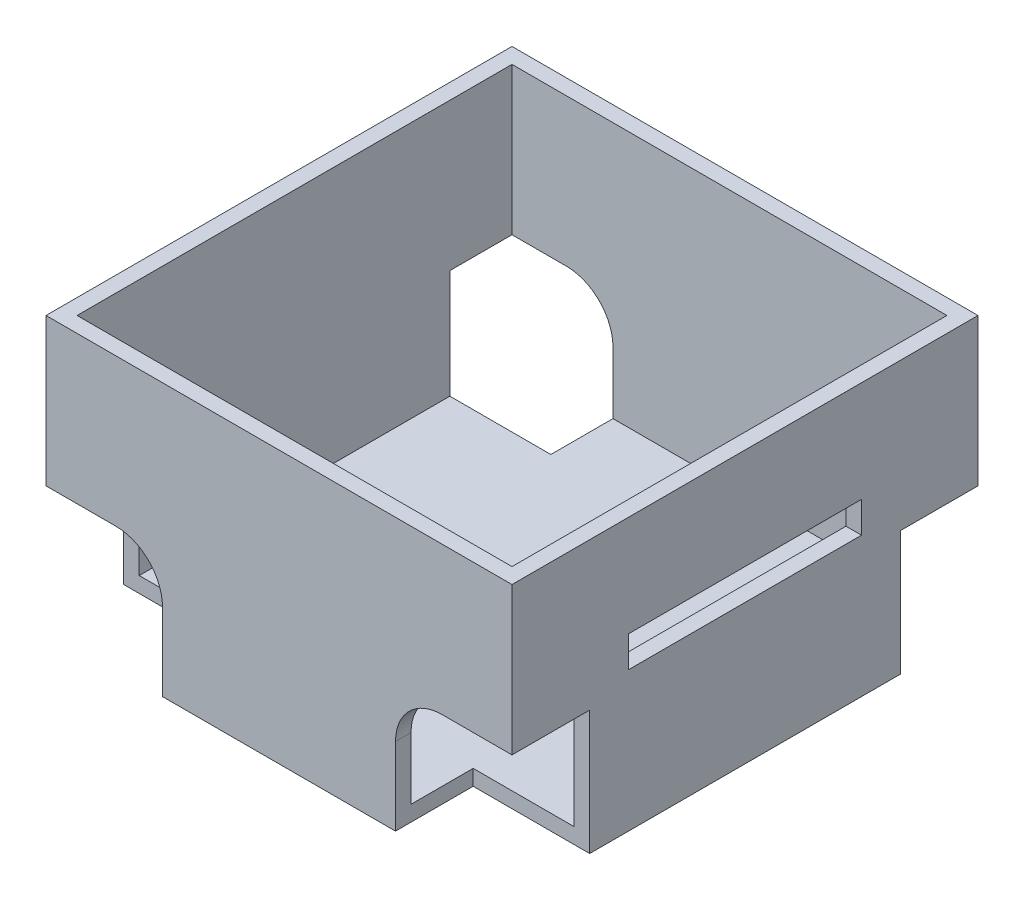
SolidWorks part; units mm, degrees
material "1060 Alloy"
ref_plane "Front Plane" through (0, 0, 0) normal (0, 0, 1) x (1, 0, 0)
ref_plane "Top Plane" through (0, 0, 0) normal (0, 1, 0) x (1, 0, 0)
ref_plane "Right Plane" through (0, 0, 0) normal (1, 0, 0) x (0, 0, -1)
sketch "Sketch1" plane through (0, 0, 0) normal (0, 1, 0) x (1, 0, 0)
  line L1 (-150, -150) -> (150, -150)
  line L2 (-150, -150) -> (-150, 150)
  line L3 (-150, 150) -> (150, 150)
  line L4 (150, -150) -> (150, 150)
  line L5 (-150, -150) -> (150, 150) construction
  line L6 (-150, 150) -> (150, -150) construction
  point P0 (0, 0)
  dimension "D2" = 300
extrude "Boss-Extrude1" add sketch "Sketch1" along normal blind 175
shell "Shell1" thickness 10 removed face at (0, 175, 0)
sketch "Sketch4" plane through (0, 0, 150) normal (0, 0, 1) x (1, 0, 0)
  line L0 (0, 0) -> (75, 0)
  line L1 (-150, 0) -> (150, 0) construction
  line L2 (75, 0) -> (75, 50)
  line L3 (105, 80) -> (150, 80)
  line L4 (150, 175) -> (150, 0) construction
  line L5 (0, 0) -> (-75, 0)
  line L6 (-75, 0) -> (-75, 50)
  line L7 (-105, 80) -> (-150, 80)
  line L8 (-150, 175) -> (-150, 0) construction
  line L9 (-150, 80) -> (-150, -5)
  line L10 (-150, -5) -> (150, -5)
  line L11 (150, -5) -> (150, 80)
  arc A0 (75, 50) -> (105, 80) centre (105, 50) cw
  arc A1 (-75, 50) -> (-105, 80) centre (-105, 50) ccw
  dimension "D6" = 30
  dimension "D1" = 80
  dimension "D2" = 80
  dimension "D3" = 75
  dimension "D4" = 75
  dimension "D5" = 5
extrude "Cut-Extrude5" cut sketch "Sketch4" against normal blind 50
sketch "Sketch7" plane through (0, 0, -150) normal (0, 0, -1) x (-1, 0, 0)
  line L0 (0, 0) -> (75, 0)
  line L1 (75, 0) -> (75, 50)
  line L2 (105, 80) -> (150, 80)
  line L3 (0, 0) -> (-75, 0)
  line L4 (-75, 0) -> (-75, 50)
  line L5 (-105, 80) -> (-150, 80)
  line L6 (-150, 80) -> (-150, -5)
  line L7 (-150, -5) -> (150, -5)
  line L8 (150, -5) -> (150, 80)
  line L9 (150, 175) -> (150, 0) construction
  line L10 (-150, 0) -> (150, 0) construction
  line L11 (-150, 175) -> (-150, 0) construction
  arc A0 (75, 50) -> (105, 80) centre (105, 50) cw
  arc A1 (-75, 50) -> (-105, 80) centre (-105, 50) ccw
  dimension "D4" = 30
  dimension "D1" = 75
  dimension "D2" = 75
  dimension "D3" = 5
  dimension "D5" = 80
  dimension "D6" = 80
extrude "Cut-Extrude6" cut sketch "Sketch7" against normal blind 50
sketch "Sketch8" plane through (150, 0, 0) normal (1, 0, 0) x (0, 0, -1)
  line L0 (0, 100) -> (0, 0) construction
  line L1 (75, 90) -> (-75, 90)
  line L2 (75, 90) -> (75, 110)
  line L3 (75, 110) -> (-75, 110)
  line L4 (-75, 90) -> (-75, 110)
  line L5 (75, 90) -> (-75, 110) construction
  line L6 (75, 110) -> (-75, 90) construction
  line L7 (0, 0) -> (0, 100)
  point P0 (0, 100)
  dimension "D1" = 150
  dimension "D2" = 100
  dimension "D3" = 20
extrude "Cut-Extrude7" cut sketch "Sketch8" against normal up to next and the other way through all contours L4 L1 L2 L3 region at (150, 91.5133, -37.5)
